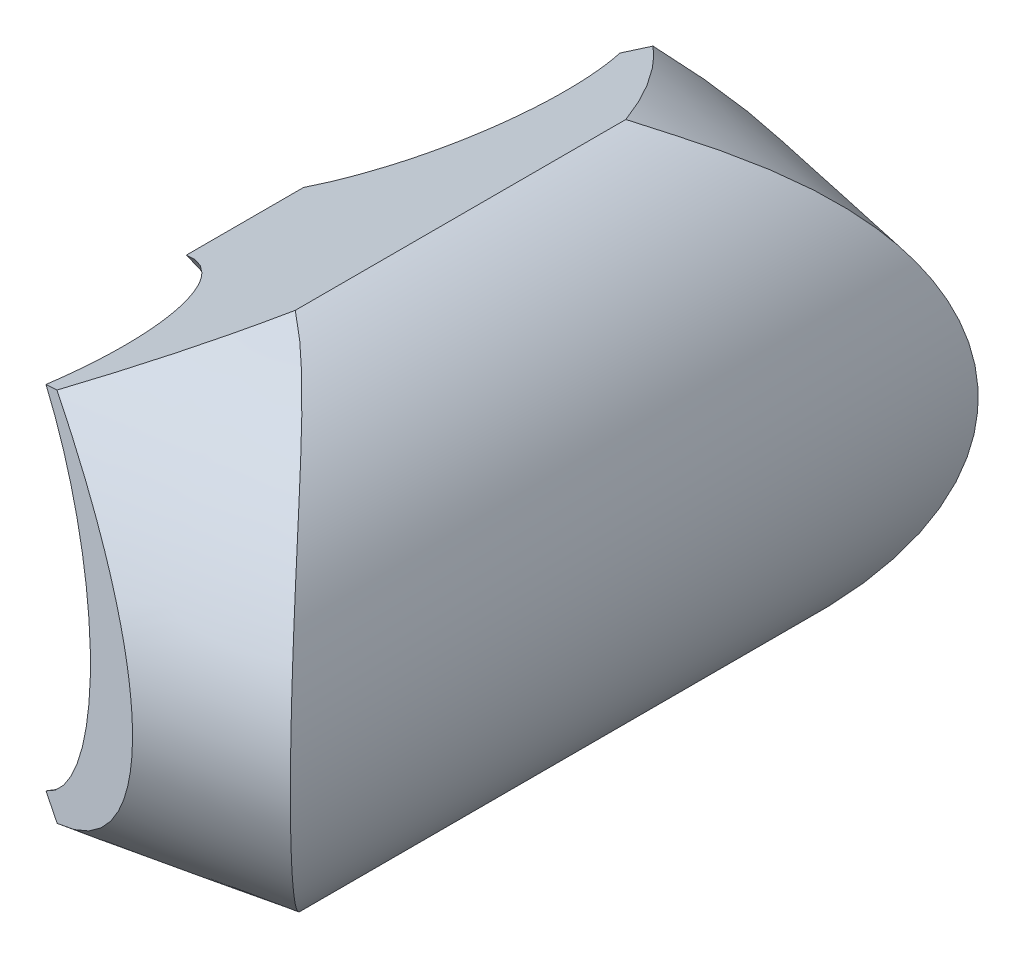
SolidWorks part; units mm, degrees
ref_plane "Front Plane" through (0, 0, 0) normal (0, 0, 1) x (1, 0, 0)
ref_plane "Top Plane" through (0, 0, 0) normal (0, 1, 0) x (1, 0, 0)
ref_plane "Right Plane" through (0, 0, 0) normal (1, 0, 0) x (0, 0, -1)
sketch "Sketch1" plane through (0, 0, 0) normal (1, 0, 0) x (0, 0, -1)
  line L0 (-1000, 0) -> (49000, 0) construction
  ellipse E0 centre (0, 0) end of major axis (167.64, 0) minor radius 111.76
  dimension "D1" = 335.28
  dimension "D2" = 223.52
ref_plane "Plane2" through (152.4, 0, 0) normal (1, 0, 0) x (0, 0, -1)
sketch "Sketch2" plane through (152.4, 0, 0) normal (1, 0, 0) x (0, 0, -1)
  line L0 (-201000, 0) -> (249000, 0) construction
  ellipse E0 centre (0, 0) end of major axis (134.62, 0) minor radius 100.33
  dimension "D1" = 269.24
  dimension "D2" = 200.66
loft "Loft1" add profiles "Sketch1", "Sketch2" connector at (0, -103.7299, 62.3973) connector at (152.4, -94.3108, 45.9266)
sketch "Sketch3" plane through (0, 0, 0) normal (-1, 0, 0) x (0, 0, 1)
  line L0 (-1000, 0) -> (49000, 0) construction
  line L1 (86.36, -1000) -> (86.36, 49000) construction
  line L2 (0, -1000) -> (0, 49000) construction
  line L3 (86.36, 81.28) -> (86.36, -81.28)
  line L4 (5.08, -990.5038) -> (5.08, 49009.4962) construction
  arc A0 (86.36, 81.28) -> (86.36, -81.28) centre (86.36, 0) ccw
  dimension "D1" = 162.56
  dimension "D2" = 5.08
  dimension "D3" = 86.36
revolve "Cut-Revolve2" cut sketch "Sketch3" angle 360 about L3
sketch "Sketch7" plane through (0, 0, 0) normal (0, 0, 1) x (1, 0, 0)
  line L0 (101.6, -995.1587) -> (101.6, 49004.8413) construction
  line L1 (0, 50.8) -> (0, -50.8)
  line L2 (0, 81.28) -> (0, -81.28) construction
  line L3 (101.6, 129.5268) -> (101.6, 104.1268)
  line L4 (0, 50.8) -> (101.6, 104.1268)
  line L5 (101.6, 129.5268) -> (-10, 129.5268)
  line L6 (-10, 129.5268) -> (-10, -129.5268)
  line L7 (0, -50.8) -> (101.6, -104.1268)
  line L8 (101.6, -104.1268) -> (101.6, -129.5268)
  line L9 (101.6, -129.5268) -> (-10, -129.5268)
  line L10 (152.4, -100.33) -> (152.4, 100.33) construction
  line L11 (0, 111.76) -> (0, -111.76) construction
  spline S9 degree 3 poles (0, -111.76) (2.985, -111.5351) (7.8521, -111.1683) (15.1479, -110.6189) (20.5476, -110.2124) (26.4411, -109.7688) (31.3571, -109.3989) (37.2691, -108.9543) (42.6277, -108.5514) (48.0663, -108.1426) (53.7653, -107.7144) (58.731, -107.3415) (64.4582, -106.9115) (69.0491, -106.5669) (73.3331, -106.2455) (76.0928, -106.0384) (78.8469, -105.8319) (82.0286, -105.5933) (85.6952, -105.3184) (90.4247, -104.9639) (95.0751, -104.6155) (100.5548, -104.205) (105.0467, -103.8687) (110.708, -103.445) (115.6614, -103.0744) (121.168, -102.6625) (126.2062, -102.2859) (131.2844, -101.9064) (136.791, -101.495) (141.5737, -101.1379) (147.0585, -100.7285) (150.2832, -100.4879) (152.4, -100.33) knots 0 0 0 0 0.058761 0.095813 0.14362 0.165058 0.211829 0.240394 0.281437 0.317315 0.347454 0.393623 0.415065 0.460195 0.483996 0.499395 0.51452 0.538211 0.562026 0.586697 0.63131 0.653569 0.694565 0.719733 0.76501 0.79207 0.828129 0.864187 0.892032 0.936524 0.958332 1 1 1 1 construction
  spline S25 degree 3 poles (152.4, 100.33) (150.2844, 100.4878) (147.2994, 100.7105) (142.5509, 101.065) (137.8971, 101.4124) (132.857, 101.7889) (127.265, 102.2067) (122.5058, 102.5625) (116.717, 102.9954) (112.1563, 103.3366) (106.5666, 103.7549) (102.0746, 104.0912) (96.3197, 104.5222) (91.4031, 104.8906) (85.866, 105.3056) (80.5063, 105.7074) (75.7338, 106.0653) (70.4464, 106.462) (65.9254, 106.8013) (60.189, 107.232) (54.7687, 107.6391) (49.3812, 108.0438) (43.6449, 108.4749) (38.8804, 108.8331) (32.9638, 109.2781) (28.0071, 109.651) (22.0957, 110.0958) (17.5461, 110.4383) (13.1823, 110.7669) (9.6118, 111.0358) (5.2023, 111.368) (2.0029, 111.6091) (0, 111.76) knots 0 0 0 0 0.041644 0.058758 0.093473 0.133253 0.157971 0.203548 0.226936 0.271922 0.293325 0.336969 0.360346 0.406608 0.433753 0.469344 0.512114 0.527698 0.573426 0.601112 0.640618 0.680125 0.707166 0.75354 0.773914 0.823636 0.851115 0.890284 0.913196 0.937018 0.960573 1 1 1 1 construction
  dimension "D1" = 101.6
  dimension "D2" = 25.4
  dimension "D3" = 25.4
  dimension "D4" = 50.8
  dimension "D5" = 10
extrude "Cut-Extrude4" cut sketch "Sketch7" against normal through all and the other way through all
mirror "Mirror5" about plane through (0, 0, 0) normal (0, 0, 1) of "Cut-Revolve2"
sketch "Sketch9" plane through (0, 0, 0) normal (0, 1, 0) x (1, 0, 0)
  line L0 (0, 95.25) -> (0, -95.25)
  line L1 (0, 95.25) -> (101.6, 145.6076)
  line L2 (101.6, -171.0076) -> (101.6, -145.6076)
  line L3 (101.6, -171.0076) -> (-10, -171.0076)
  line L4 (-10, -171.0076) -> (-10, 171.0076)
  line L5 (101.6, -995.0141) -> (101.6, 49004.9859) construction
  line L6 (-1000, 0) -> (49000, 0) construction
  line L7 (101.6, 171.0076) -> (101.6, 145.6076)
  line L8 (101.6, 171.0076) -> (-10, 171.0076)
  line L9 (0, -95.25) -> (101.6, -145.6076)
  line L11 (152.4, -122.936) -> (152.4, 122.936) construction
  spline S9 degree 3 poles (33.6981, -160.3254) (34.8566, -160.074) (37.3047, -159.5429) (41.1159, -158.7161) (44.8415, -157.9079) (48.2434, -157.1701) (51.3786, -156.4902) (53.8435, -155.9556) (55.7046, -155.5521) (57.0693, -155.2562) (58.692, -154.9043) (61.0691, -154.389) (63.8259, -153.7913) (67.0265, -153.0975) (70.3556, -152.3759) (73.5414, -151.6855) (76.9849, -150.9393) (80.2854, -150.2241) (85.0142, -149.1996) (89.2158, -148.2895) (94.7551, -147.0898) (100.2685, -145.8959) (105.7833, -144.702) (110.2202, -143.7416) (113.5207, -143.0273) (118.0409, -142.0491) (122.2435, -141.1399) (127.545, -139.9931) (132.6262, -138.8941) (138.1869, -137.6918) (142.6124, -136.7351) (147.2461, -135.7336) (150.3562, -135.0616) (152.4, -134.62) knots 0 0 0 0 0.029282 0.061878 0.09633 0.123446 0.147861 0.175575 0.185746 0.1949 0.210067 0.226758 0.254982 0.279743 0.307651 0.339124 0.36026 0.394683 0.422541 0.479775 0.500875 0.562537 0.619117 0.640251 0.674671 0.70253 0.754488 0.780879 0.836511 0.8829 0.921406 0.948351 1 1 1 1 construction
  point P8 (-10, 0)
  point P19 (0, 0)
  dimension "D1" = 95.25
  dimension "D2" = 10
  dimension "D3" = 50.8
  dimension "D4" = 25.4
extrude "Cut-Extrude5" cut sketch "Sketch9" against normal through all and the other way through all
sketch "Sketch11" plane through (0, 0, 0) normal (0, 0, 1) x (1, 0, 0)
  line L0 (152.4, -100.33) -> (152.4, 100.33) construction
  line L1 (-1000, 0) -> (49000, 0) construction
  line L3 (52.07, 100.33) -> (52.07, 115.33)
  line L4 (52.07, 115.33) -> (162.4, 115.33)
  line L5 (162.4, 115.33) -> (162.4, -115.33)
  line L6 (162.4, -115.33) -> (52.07, -115.33)
  line L7 (52.07, -115.33) -> (52.07, -100.33)
  line L8 (152.4, -122.936) -> (152.4, 122.936) construction
  arc A0 (52.07, -100.33) -> (52.07, 100.33) centre (52.07, 0) ccw
  dimension "D1" = 200.66
  dimension "D2" = 10
  dimension "D3" = 15
  dimension "D4" = 15
  dimension "D5" = 52.07
extrude "Cut-Extrude6" cut sketch "Sketch11" against normal through all and the other way through all
sketch3d "3DSketch1"
  line L0 (0, 0, 86.36) -> (0, 0, -86.36)
  line L1 (0, 0, 0) -> (152.4, 0, 0)
  line L2 (52.07, 0, -190.5) -> (52.07, 0, 190.5)
  line L3 (52.07, -127, 0) -> (52.07, 127, 0)
  point P7 (52.07, 0, 0)
  dimension "D1" = 172.72
  dimension "D2" = 381
  dimension "D3" = 52.07
  dimension "D4" = 254
